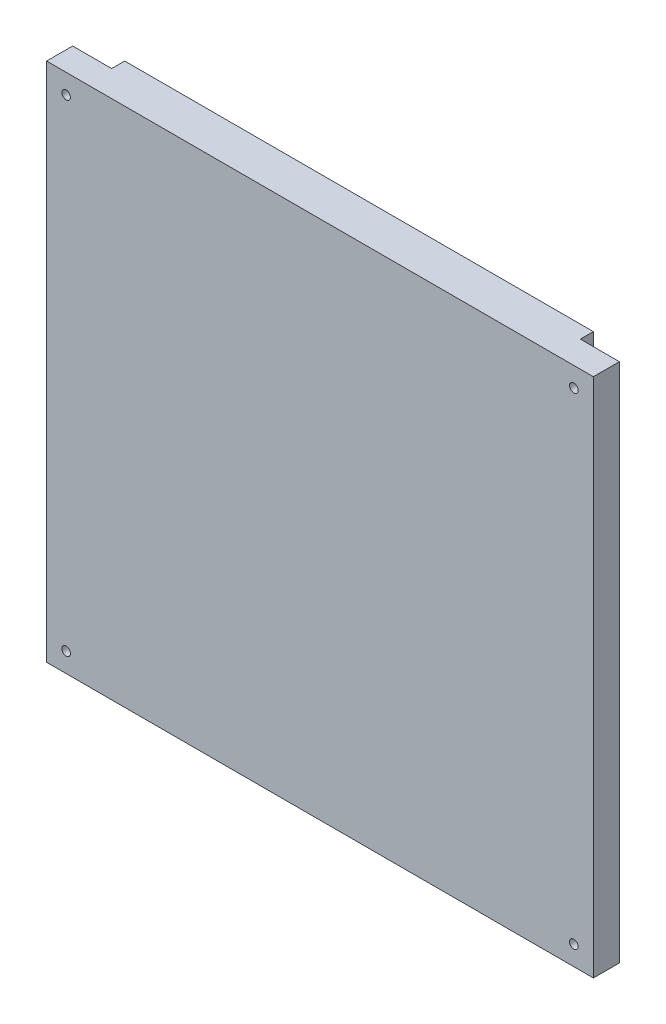
SolidWorks part; units mm, degrees
ref_plane "Front Plane" through (0, 0, 0) normal (0, 0, 1) x (1, 0, 0)
ref_plane "Top Plane" through (0, 0, 0) normal (0, 1, 0) x (1, 0, 0)
ref_plane "Right Plane" through (0, 0, 0) normal (1, 0, 0) x (0, 0, -1)
sketch "Sketch3" plane through (0, 0, 0) normal (0, 1, 0) x (1, 0, 0)
  line L0 (-105, 0) -> (105, 0)
  line L1 (105, 0) -> (105, -10)
  line L2 (105, -10) -> (-105, -10)
  line L3 (-105, -10) -> (-105, 0)
  dimension "D1" = 210
  dimension "D2" = 10
extrude "Boss-Extrude1" add sketch "Sketch3" along normal blind 200
ref_plane "Plane1" through (0, 30, 0) normal (0, 1, 0) x (1, 0, 0)
sketch "Sketch5" plane through (0, 200, 0) normal (0, 1, 0) x (1, 0, 0)
  line L0 (-90, 0) -> (-90, 5)
  line L1 (105, 0) -> (-105, 0) construction
  line L2 (-90, 5) -> (90, 5)
  line L3 (90, 5) -> (90, 0)
  line L4 (-105, 0) -> (-105, -10) construction
  line L5 (105, 0) -> (90, 0)
  line L9 (-105, 0) -> (-105, -10)
  line L10 (-105, -10) -> (105, -10)
  line L11 (105, -10) -> (105, 0)
  line L12 (105, 0) -> (-105, 0)
  line L13 (-105, 0) -> (-105, -10)
  line L14 (-105, -10) -> (105, -10)
  line L15 (105, -10) -> (105, 0)
  line L16 (-90, 0) -> (-105, 0)
  dimension "D1" = 180
  dimension "D2" = 5
  dimension "D3" = 15
  dimension "D4" = 0
extrude "Boss-Extrude2" add sketch "Sketch5" against normal up to surface (170 mm away) up to plane "Plane1"
sketch "Sketch6" plane through (0, 30, 0) normal (0, 1, 0) x (1, 0, 0)
  line L0 (-80, 0) -> (-80, 15)
  line L2 (-80, 15) -> (80, 15)
  line L3 (80, 15) -> (80, 0)
  line L4 (80, 0) -> (-80, 0)
  line L6 (90, 5) -> (-90, 5) construction
  point P2 (-76.4956, -0.7485)
  point P8 (0, 0)
  point P9 (0, 0)
  point P10 (-76.9672, 10)
  dimension "D1" = 160
  dimension "D2" = 10
extrude "Boss-Extrude3" add sketch "Sketch6" against normal blind 10
sketch "Sketch7" plane through (0, 0, 10) normal (0, 0, 1) x (1, 0, 0)
  line L0 (0, -1000) -> (0, 49000) construction
  line L1 (-105, 200) -> (105, 200) construction
  line L2 (-105, 200) -> (-105, 0) construction
  line L3 (5.5, 0) -> (-5.5, 0) construction
  circle A0 centre (-97.5, 192.5) radius 1.65
  circle A1 centre (-97.5, 7.5) radius 1.65
  circle A2 centre (97.5, 7.5) radius 1.65
  circle A3 centre (97.5, 192.5) radius 1.65
  dimension "D1" = 3.3
  dimension "D2" = 7.5
  dimension "D4" = 7.5
  dimension "D3" = 7.5
  dimension "D5" = 7.5
extrude "Cut-Extrude1" cut sketch "Sketch7" against normal up to surface (10 mm away) up to face at (0, 80, 0)
